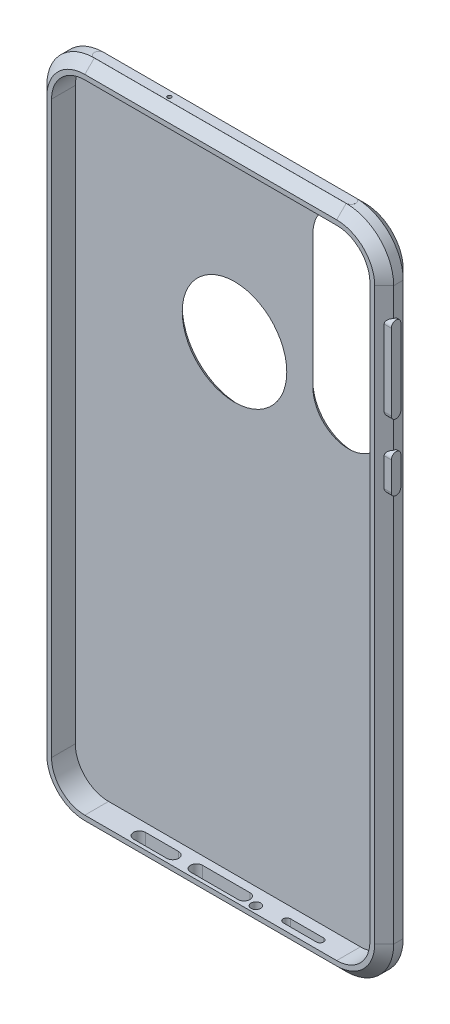
SolidWorks part; units mm, degrees
ref_plane "Front Plane" through (0, 0, 0) normal (0, 0, 1) x (1, 0, 0)
ref_plane "Top Plane" through (0, 0, 0) normal (0, 1, 0) x (1, 0, 0)
ref_plane "Right Plane" through (0, 0, 0) normal (1, 0, 0) x (0, 0, -1)
sketch "Sketch1" plane through (0, 0, 0) normal (0, 0, 1) x (1, 0, 0)
  line L1 (-26.5, 70) -> (26.5, 70)
  line L2 (-36.5, 60) -> (-36.5, -60)
  line L3 (-26.5, -70) -> (26.5, -70)
  line L4 (36.5, 60) -> (36.5, -60)
  line L5 (-36.5, 70) -> (36.5, -70) construction
  line L6 (-36.5, -70) -> (36.5, 70) construction
  arc A0 (26.5, 70) -> (36.5, 60) centre (26.5, 60) cw
  arc A1 (36.5, -60) -> (26.5, -70) centre (26.5, -60) cw
  arc A2 (-26.5, -70) -> (-36.5, -60) centre (-26.5, -60) cw
  arc A3 (-36.5, 60) -> (-26.5, 70) centre (-26.5, 60) cw
  point P0 (0, 0)
  dimension "D3" = 10
  dimension "D1" = 140
  dimension "D2" = 73
extrude "Boss-Extrude1" add sketch "Sketch1" along normal blind 6
sketch "Sketch2" plane through (0, 0, 0) normal (0, 0, -1) x (-1, 0, 0)
  line L0 (-26.5, 70) -> (26.5, 70) construction
  line L3 (-24, 58) -> (-24, 30) construction
  line L4 (-16.5, 58) -> (-16.5, 30)
  line L5 (-31.5, 58) -> (-31.5, 30)
  line L6 (-36.5, -60) -> (-36.5, 60) construction
  circle A0 centre (0, 30) radius 8
  arc A1 (-16.5, 58) -> (-31.5, 58) centre (-24, 58) ccw
  arc A2 (-31.5, 30) -> (-16.5, 30) centre (-24, 30) ccw
  point P4 (-24, 44)
  dimension "D1" = 16
  dimension "D6" = 12
  dimension "D3" = 15
  dimension "D4" = 28
  dimension "D5" = 5
extrude "Cut-Extrude1" cut sketch "Sketch2" against normal through all
chamfer "Chamfer1" distance 4 angle 45 1 edges at (-8, 30, 0)
chamfer "Chamfer2" distance 1 angle 45 4 edges at (24, 22.5, 0) (31.5, 44, 0) (24, 65.5, 0) (16.5, 44, 0)
chamfer "Chamfer3" distance 2 angle 45 8 edges at (-33.5711, -67.0711, 0) (0, -70, 0) (33.5711, -67.0711, 0) (-36.5, 0, 0) (-33.5711, 67.0711, 0) (0, 70, 0) (33.5711, 67.0711, 0) (36.5, 0, 0)
sketch "Sketch3" plane through (36.5, 0, 0) normal (1, 0, 0) x (0, 0, -1)
  line L0 (-4, 60) -> (-4, -60) construction
  line L1 (-6, 60) -> (-2, 60) construction
  line L2 (-6, -60) -> (-2, -60) construction
  line L3 (-4, 23) -> (-4, 29) construction
  line L4 (-5, 23) -> (-5, 29)
  line L5 (-3, 23) -> (-3, 29)
  line L6 (-4, 37) -> (-4, 53) construction
  line L7 (-5, 37) -> (-5, 53)
  line L8 (-3, 37) -> (-3, 53)
  arc A0 (-5, 23) -> (-3, 23) centre (-4, 23) ccw
  arc A1 (-3, 29) -> (-5, 29) centre (-4, 29) ccw
  arc A2 (-5, 37) -> (-3, 37) centre (-4, 37) ccw
  arc A3 (-3, 53) -> (-5, 53) centre (-4, 53) ccw
  point P8 (-4, 26)
  point P15 (-4, 45)
  dimension "D2" = 83
  dimension "D3" = 8
  dimension "D6" = 2
  dimension "D1" = 2
  dimension "D4" = 6
  dimension "D5" = 16
extrude "Boss-Extrude2" add sketch "Sketch3" along normal blind 0.5
sketch "Sketch4" plane through (0, -70, 0) normal (0, -1, 0) x (1, 0, 0)
  line L0 (-26.5, 4) -> (26.5, 4) construction
  line L1 (-26.5, 6) -> (-26.5, 2) construction
  line L2 (26.5, 6) -> (26.5, 2) construction
  line L3 (0, 6) -> (0, 2) construction
  line L4 (-26.5, 6) -> (26.5, 6) construction
  line L5 (-26.5, 2) -> (26.5, 2) construction
  line L6 (-5, 4) -> (5, 4) construction
  line L7 (-5, 5.25) -> (5, 5.25)
  line L8 (-5, 2.75) -> (5, 2.75)
  line L9 (-17, 4) -> (-10, 4) construction
  line L10 (-17, 5.25) -> (-10, 5.25)
  line L11 (-17, 2.75) -> (-10, 2.75)
  line L12 (14, 4) -> (21, 4) construction
  line L13 (14, 4.75) -> (21, 4.75)
  line L14 (14, 3.25) -> (21, 3.25)
  arc A0 (-5, 5.25) -> (-5, 2.75) centre (-5, 4) ccw
  arc A1 (5, 2.75) -> (5, 5.25) centre (5, 4) ccw
  arc A2 (-17, 5.25) -> (-17, 2.75) centre (-17, 4) ccw
  arc A3 (-10, 2.75) -> (-10, 5.25) centre (-10, 4) ccw
  circle A4 centre (8, 4.5) radius 1
  arc A5 (14, 4.75) -> (14, 3.25) centre (14, 4) ccw
  arc A6 (21, 3.25) -> (21, 4.75) centre (21, 4) ccw
  point P11 (0, 4)
  point P20 (-13.5, 4)
  point P31 (17.5, 4)
  dimension "D6" = 2
  dimension "D7" = 3
  dimension "D8" = 1.5
  dimension "D11" = 6
  dimension "D1" = 10
  dimension "D2" = 2.5
  dimension "D3" = 2.5
  dimension "D4" = 7
  dimension "D5" = 5
  dimension "D9" = 7
  dimension "D10" = 1.5
chamfer "Chamfer4" distance 2 angle 45 8 edges at (33.5711, 67.0711, 6) (0, 70, 6) (-33.5711, 67.0711, 6) (-36.5, 0, 6) (-33.5711, -67.0711, 6) (36.5, 0, 6) (33.5711, -67.0711, 6) (0, -70, 6)
extrude "Cut-Extrude3" cut sketch "Sketch4" against normal blind 50
sketch "Sketch5" plane through (0, 70, 0) normal (0, 1, 0) x (1, 0, 0)
  line L0 (-26.5, -3) -> (26.5, -3) construction
  line L1 (-26.5, -4) -> (-26.5, -2) construction
  line L2 (26.5, -4) -> (26.5, -2) construction
  line L3 (0, -2) -> (0, -4) construction
  line L4 (26.5, -2) -> (-26.5, -2) construction
  line L5 (-26.5, -4) -> (26.5, -4) construction
  line L6 (-26.5, -3) -> (26.5, -3) construction
  line L7 (-26.5, -2) -> (26.5, -2)
  line L8 (-26.5, -4) -> (26.5, -4)
  arc A0 (-26.5, -2) -> (-26.5, -4) centre (-26.5, -3) ccw
  arc A1 (26.5, -4) -> (26.5, -2) centre (26.5, -3) ccw
  point P12 (0, -3)
  dimension "D1" = 2
extrude "Boss-Extrude3" add sketch "Sketch5" along normal blind 0.01
sketch "Sketch6" plane through (0, 70.01, 0) normal (0, 1, 0) x (1, 0, 0)
  line L0 (-26.5, -3) -> (26.5, -3) construction
  line L1 (0, -2) -> (0, -4) construction
  line L2 (26.5, -2) -> (-26.5, -2) construction
  line L3 (-26.5, -4) -> (26.5, -4) construction
  line L4 (-26.5, -4) -> (26.5, -4) construction
  circle A0 centre (-11.5, -3.2) radius 0.4
  arc A1 (-26.5, -2) -> (-26.5, -4) centre (-26.5, -3) ccw construction
  dimension "D1" = 0.8
  dimension "D2" = 0.8
  dimension "D3" = 15
extrude "Cut-Extrude5" cut sketch "Sketch6" against normal blind 50
sketch "Sketch7" plane through (0, 0, 6) normal (0, 0, 1) x (1, 0, 0)
  line L9 (33.5, -60) -> (33.5, 60)
  line L10 (26.5, 67) -> (-26.5, 67)
  line L11 (-33.5, 60) -> (-33.5, -60)
  line L12 (-26.5, -67) -> (26.5, -67)
  line L13 (33.5, -60) -> (33.5, 60)
  line L14 (26.5, 67) -> (-26.5, 67)
  line L15 (-33.5, 60) -> (-33.5, -60)
  line L16 (-26.5, -67) -> (26.5, -67)
  arc A8 (33.5, 60) -> (26.5, 67) centre (26.5, 60) ccw
  arc A9 (-26.5, 67) -> (-33.5, 60) centre (-26.5, 60) ccw
  arc A10 (-33.5, -60) -> (-26.5, -67) centre (-26.5, -60) ccw
  arc A11 (26.5, -67) -> (33.5, -60) centre (26.5, -60) ccw
  arc A12 (33.5, 60) -> (26.5, 67) centre (26.5, 60) ccw
  arc A13 (-26.5, 67) -> (-33.5, 60) centre (-26.5, 60) ccw
  arc A14 (-33.5, -60) -> (-26.5, -67) centre (-26.5, -60) ccw
  arc A15 (26.5, -67) -> (33.5, -60) centre (26.5, -60) ccw
  dimension "D1" = 1
extrude "Cut-Extrude7" cut sketch "Sketch7" against normal blind 5
